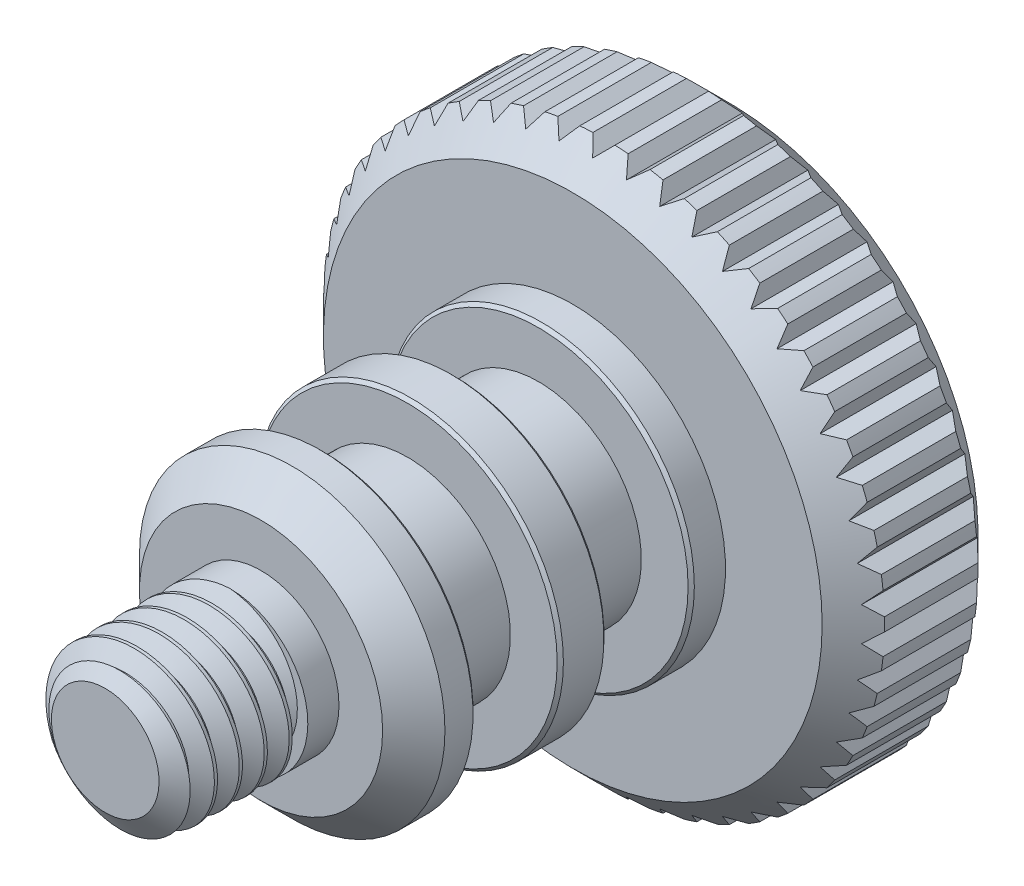
SolidWorks part; units mm, degrees
material "1060 Alloy"
ref_plane "Front Plane" through (0, 0, 0) normal (0, 0, 1) x (1, 0, 0)
ref_plane "Top Plane" through (0, 0, 0) normal (0, 1, 0) x (1, 0, 0)
ref_plane "Right Plane" through (0, 0, 0) normal (1, 0, 0) x (0, 0, -1)
sketch "Sketch1" plane through (0, 0, 0) normal (1, 0, 0) x (0, 0, -1)
  line L0 (0, 0) -> (0, 4.9)
  line L1 (0, 4.9) -> (2, 4.9)
  line L2 (2, 4.9) -> (2, 3.3)
  line L3 (2, 3.3) -> (4.7, 3.3)
  line L4 (4.7, 3.3) -> (4.7, 4.9)
  line L5 (4.7, 4.9) -> (6.2, 4.9)
  line L6 (6.2, 4.9) -> (6.2, 3.3)
  line L7 (6.2, 3.3) -> (8.9, 3.3)
  line L8 (8.9, 3.3) -> (8.9, 4.9)
  line L9 (8.9, 4.9) -> (10, 4.9)
  line L11 (15, 0) -> (0, 0)
  line L12 (0, 4.9) -> (0, 5) construction
  line L13 (0, 5) -> (8.9, 5) construction
  line L14 (8.9, 5) -> (8.9, 4.9) construction
  line L15 (10, 4.9) -> (10, 9)
  line L17 (10, 9) -> (15, 9)
  line L18 (15, 9) -> (15, 0)
  circle A0 centre (3, 4.3) radius 1 construction
  circle A1 centre (7.2, 4.3) radius 1 construction
  dimension "D6" = 2
  dimension "D1" = 4.9
  dimension "D2" = 2.7
  dimension "D3" = 10
  dimension "D4" = 2
  dimension "D5" = 1.5
  dimension "D7" = 5
  dimension "D8" = 1.7
  dimension "D9" = 5
  dimension "D11" = 9
revolve "Revolve1" add sketch "Sketch1" angle 360 about L11
chamfer "Chamfer1" distance 1 angle 45 3 edges at (-9, 0, -10) (-4.9, 0, 0) (-9, 0, -15)
chamfer "Chamfer2" distance 0.1 angle 45 4 edges at (-4.9, 0, -8.9) (-4.9, 0, -6.2) (-4.9, 0, -4.7) (-4.9, 0, -2)
sketch "Sketch2" plane through (0, 0, -15) normal (0, 0, -1) x (-1, 0, 0)
  line L0 (0, 8.6395) -> (-0.3536, 8.9931)
  line L1 (-0.3536, 8.9931) -> (0, 9.3466)
  line L2 (0, 9.3466) -> (0.3536, 8.9931)
  line L3 (0.3536, 8.9931) -> (0, 8.6395)
  circle A0 centre (0, 0) radius 9 construction
  dimension "D1" = 0.5
extrude "Cut-Extrude1" cut sketch "Sketch2" against normal through all
pattern_circular "CirPattern1" count 50 over 360 about axis through (0, 0, -15) along (0, 0, -1) of "Cut-Extrude1"
sketch "Sketch3" plane through (0, 0, 0) normal (0, 0, 1) x (1, 0, 0)
  circle A0 centre (0, 0) radius 2.5
  dimension "D1" = 5
extrude "Boss-Extrude1" add sketch "Sketch3" along normal blind 5
sketch "Sketch4" plane through (0, 0, 0) normal (1, 0, 0) x (0, 0, -1)
  line L0 (-5, 2.5) -> (-5.3, 1.9804)
  line L1 (-5.3, 1.9804) -> (-5.4, 1.9804)
  line L2 (-5.4, 1.9804) -> (-5.7, 2.5)
  line L3 (-5.7, 2.5) -> (-5, 2.5)
  line L4 (-5.55, 2.2402) -> (-5.15, 2.2402) construction
  dimension "D1" = 60
  dimension "D2" = 0.1
  dimension "D3" = 0.4
sketch "Sketch5" plane through (0, 0, 5) normal (0, 0, 1) x (1, 0, 0)
  circle A0 centre (0, 0) radius 2.5 construction
  circle A1 centre (0, 0) radius 2.5
curve "Helix/Spiral1" pitch 0.8 height 4.7 radius 2.5 centre (0, 0, 5) axis (0, 0, -1) start towards (0, 1, 0)
sweep "Cut-Sweep1" cut profiles "Sketch4" path "Helix/Spiral1" align with end faces yes
sketch "Sketch6" plane through (0, 0, 0) normal (1, 0, 0) x (0, 0, -1)
  line L0 (-5, 1.7264) -> (-4.4583, 2.5)
  line L1 (-5, 2.5) -> (-5, -1.4003) construction
  line L2 (-4.4583, 2.5) -> (-5, 2.5)
  line L3 (-5, 2.5) -> (-5, 1.7264)
  line L4 (-5.3, 1.9804) -> (-5.4, 1.9804) construction
  line L5 (0, 0) -> (-5, 0) construction
  dimension "D1" = 55
  dimension "D2" = 0.254
revolve "Cut-Revolve1" cut sketch "Sketch6" angle 360 about L5
sketch "Sketch7" plane through (0, 0, 0) normal (0, 0, 1) x (1, 0, 0)
  circle A0 centre (0, 0) radius 2.5 construction
  circle A1 centre (0, 0) radius 2.5
extrude "Boss-Extrude2" add sketch "Sketch7" along normal blind 1
